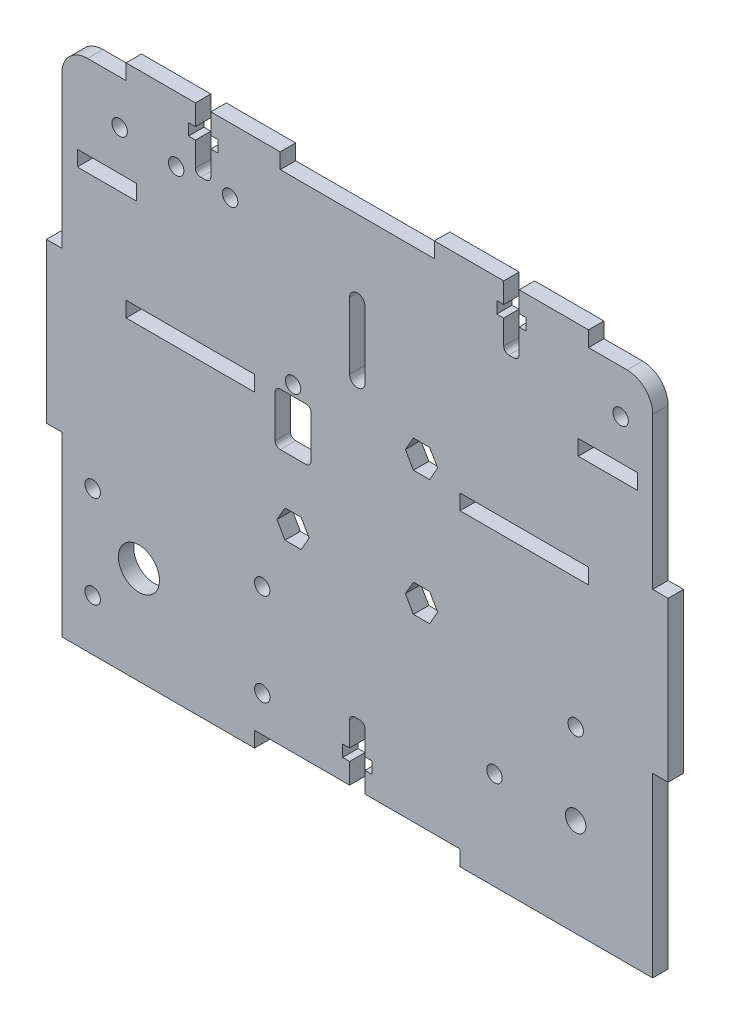
SolidWorks part; units mm, degrees
other "Marcação1"
sketch "Esboço7" plane through (-68, 31.5, 3) normal (-0.6758, 0.2828, 0.6807) x (0.7271, 0.1043, 0.6785)
sketch "Esboço8" plane through (-68, 31.5, 3) normal (-0.6758, 0.2828, 0.6807) x (0.7271, 0.1043, 0.6785)
sketch "Esboço9" plane through (-68, 31.5, 3) normal (-0.6758, 0.2828, 0.6807) x (0.7271, 0.1043, 0.6785)
sketch "Esboço10" plane through (-68, 31.5, 3) normal (-0.6758, 0.2828, 0.6807) x (0.7271, 0.1043, 0.6785)
sketch "Esboço11" plane through (-68, 36.25, 3) normal (-0.6758, 0.2828, 0.6807) x (0.7271, 0.1043, 0.6785)
sketch "Esboço13" plane through (-68, 36.25, 3) normal (-0.6758, 0.2828, 0.6807) x (0.7271, 0.1043, 0.6785)
sketch "Esboço15" plane through (-68, 36.25, 3) normal (-0.6758, 0.2828, 0.6807) x (0.7271, 0.1043, 0.6785)
sketch "Esboço19" plane through (-68, 66.25, 3) normal (-0.6758, 0.2828, 0.6807) x (0.7271, 0.1043, 0.6785)
sketch "Esboço22" plane through (-68, 95.5577, 3) normal (-0.6758, 0.2828, 0.6807) x (0.7271, 0.1043, 0.6785)
sketch "Sketch16" plane through (-60.5, 53, 1.5) normal (-0.6758, 0.2828, 0.6807) x (0.7271, 0.1043, 0.6785)
material "Acrylic (Medium-high impact)"
ref_plane "Plano frontal" through (0, 0, 0) normal (0, 0, 1) x (1, 0, 0)
ref_plane "Plano superior" through (0, 0, 0) normal (0, 1, 0) x (1, 0, 0)
ref_plane "Plano direito" through (0, 0, 0) normal (1, 0, 0) x (0, 0, -1)
sketch "Esboço1" plane through (0, 0, 0) normal (0, 0, 1) x (1, 0, 0)
  line L6 (57.5, -50) -> (-57.5, -50)
  line L8 (57.5, -50) -> (57.5, 50)
  line L9 (57.5, 50) -> (-57.5, 50)
  line L10 (-57.5, -50) -> (-57.5, 50)
  line L11 (57.5, -50) -> (-57.5, 50) construction
  line L12 (57.5, 50) -> (-57.5, -50) construction
  point P0 (0, 0)
  dimension "D1" = 100
  dimension "D2" = 115
extrude "Ressalto-extrusão1" add sketch "Esboço1" along normal mid plane 3
sketch "Esboço2" plane through (0, 0, 1.5) normal (0, 0, 1) x (1, 0, 0)
  line L1 (-20, -50) -> (20, -50)
  line L2 (-20, -50) -> (-20, -47)
  line L3 (-20, -47) -> (20, -47)
  line L4 (20, -50) -> (20, -47)
  line L6 (-57.5, -50) -> (57.5, -50) construction
  line L15 (57.5, 50) -> (-57.5, 50) construction
  line L25 (-45, 13) -> (-20, 13)
  line L26 (-45, 13) -> (-45, 10)
  line L29 (-45, 10) -> (-20, 10)
  line L30 (-20, 13) -> (-20, 10)
  line L31 (0, -1.65) -> (0, 1.65) construction
  line L32 (20, 13) -> (20, 10)
  line L33 (45, 10) -> (20, 10)
  line L34 (45, 13) -> (45, 10)
  line L35 (45, 13) -> (20, 13)
  point P6 (0, -47)
  dimension "D4" = 25
  dimension "D3" = 3
  dimension "D1" = 37
  dimension "D2" = 40
  dimension "D5" = 40
extrude "Corte-extrusão1" cut sketch "Esboço2" against normal through all
sketch "Sketch9" plane through (0, 0, 0) normal (0, 0, 1) x (1, 0, 0)
  line L0 (20, -47) -> (-20, -47) construction
  line L1 (-1.5, -47) -> (1.5, -47)
  line L2 (-1.5, -47) -> (-1.5, -43)
  line L3 (-0.5, -35) -> (0.5, -35)
  line L4 (1.5, -47) -> (1.5, -43)
  line L5 (1.5, -40.73) -> (2.85, -40.73)
  line L6 (-2.85, -40.73) -> (-1.5, -40.73)
  line L7 (-2.85, -40.73) -> (-2.85, -43)
  line L8 (-2.85, -43) -> (-1.5, -43)
  line L9 (2.85, -40.73) -> (2.85, -43)
  line L10 (-1.5, -40.73) -> (-1.5, -36)
  line L11 (1.5, -43) -> (2.85, -43)
  line L12 (1.5, -40.73) -> (1.5, -36)
  arc A0 (0.5, -35) -> (1.5, -36) centre (0.5, -36) cw
  arc A1 (-1.5, -36) -> (-0.5, -35) centre (-0.5, -36) cw
  point P6 (0, -35)
  point P18 (1.5, -35)
  point P21 (-1.5, -35)
  dimension "D7" = 1
  dimension "D1" = 3
  dimension "D2" = 12
  dimension "D3" = 2.27
  dimension "D4" = 1.35
  dimension "D5" = 1.35
  dimension "D6" = 4
extrude "Cut-Extrude12" cut sketch "Sketch9" against normal through all both and the other way through all
sketch "Esboço3" plane through (0, 0, 1.5) normal (0, 0, 1) x (1, 0, 0)
  line L0 (57.5, -50) -> (57.5, 50) construction
  line L1 (57.5, 15.5) -> (60.5, 15.5)
  line L2 (57.5, 15.5) -> (57.5, -15.5)
  line L3 (57.5, -15.5) -> (60.5, -15.5)
  line L4 (60.5, 15.5) -> (60.5, -15.5)
  line L5 (0, -1.65) -> (0, 1.65) construction
  line L6 (-57.5, -15.5) -> (-60.5, -15.5)
  line L7 (-57.5, 15.5) -> (-60.5, 15.5)
  line L8 (-57.5, 15.5) -> (-57.5, -15.5)
  line L9 (-60.5, 15.5) -> (-60.5, -15.5)
  line L15 (57.5, 50) -> (-57.5, 50) construction
  line L16 (-45, 50) -> (-15, 50)
  line L17 (-45, 50) -> (-45, 53)
  line L18 (-45, 53) -> (-15, 53)
  line L19 (-15, 50) -> (-15, 53)
  line L20 (15, 50) -> (15, 53)
  line L21 (45, 53) -> (15, 53)
  line L22 (45, 50) -> (45, 53)
  line L23 (45, 50) -> (15, 50)
  line L24 (-57.5, 50) -> (-57.5, -50) construction
  point P6 (57.5, 0)
  dimension "D1" = 3
  dimension "D2" = 31
  dimension "D3" = 30
  dimension "D4" = 15
  dimension "D5" = 12.5
extrude "Ressalto-extrusão2" add sketch "Esboço3" against normal through all
sketch "Esboço30" plane through (0, 0, -1.5) normal (0, 0, -1) x (-1, 0, 0)
  line L2 (57.5, -15.5) -> (57.5, -50) construction
  line L6 (57.5, -50) -> (20, -50) construction
  circle A1 centre (42.5, -31) radius 4
  dimension "D1" = 15
  dimension "D2" = 19
  dimension "D3" = 8
extrude "Corte-extrusão11" cut sketch "Esboço30" against normal through all both and the other way through all
sketch "Esboço4" plane through (0, 0, 1.5) normal (0, 0, 1) x (1, 0, 0)
  line L0 (57.5, -50) -> (57.5, -15.5) construction
  line L76 (-46.5, -31) -> (-38.5, -31) construction
  circle A11 centre (42.5, -31) radius 2
  circle A14 centre (-42.5, -31) radius 4 construction
  dimension "D1" = 15
  dimension "D2" = 4
extrude "Corte-extrusão2" cut sketch "Esboço4" against normal through all
sketch "Esboço31" plane through (0, 0, -1.5) normal (0, 0, -1) x (-1, 0, 0)
  line L1 (57.5, -15.5) -> (57.5, -50) construction
  line L2 (46.5, -31) -> (38.5, -31) construction
  circle A4 centre (51.5, -22) radius 1.5
  circle A5 centre (51.5, -40) radius 1.5
  circle A6 centre (42.5, -31) radius 4 construction
  circle A7 centre (18.5, -22) radius 1.5
  circle A8 centre (18.5, -40) radius 1.5
  dimension "D1" = 3
  dimension "D3" = 6
  dimension "D4" = 18
  dimension "D5" = 33
extrude "Corte-extrusão12" cut sketch "Esboço31" against normal through all both and the other way through all
sketch "Sketch8" [suppressed] plane through (0, 0, -1.5) normal (0, 0, -1) x (-1, 0, 0)
  line L31 (-57.5, 39.6519) -> (-53.4896, 39.6519)
  line L32 (-58, 31.6519) -> (-58, 23.6519) construction
  line L33 (-57.5, 23.6519) -> (-53.4896, 23.6519)
  line L34 (-45, 36.6519) -> (-45, 26.6519)
  line L35 (-57.5, 15.5) -> (-57.5, 50) construction
  line L37 (-48.5, 41.4019) -> (-50, 44)
  line L38 (-50, 44) -> (-53, 44)
  line L39 (-53, 44) -> (-54.5, 41.4019)
  line L40 (-54.5, 41.4019) -> (-53.4896, 39.6519)
  line L42 (-49.5104, 39.6519) -> (-48.5, 41.4019)
  line L43 (-49.5104, 39.6519) -> (-48, 39.6519)
  line L45 (-51.7693, 38.8038) -> (-50.2755, 38.8038) [skipped]
  line L46 (-58, 31.6519) -> (-45, 31.6519) construction
  line L48 (-49.5104, 23.6519) -> (-48.5, 21.9019)
  line L49 (-54.5, 21.9019) -> (-53.4896, 23.6519)
  line L50 (-53, 19.3038) -> (-54.5, 21.9019)
  line L51 (-50, 19.3038) -> (-53, 19.3038)
  line L52 (-48.5, 21.9019) -> (-50, 19.3038)
  line L53 (-49.5104, 23.6519) -> (-48, 23.6519)
  line L54 (-57.5, 23.6519) -> (-57.5, 39.6519)
  line L55 (-58, 39.6519) -> (-57.5, 39.6519) construction
  line L56 (-58, 39.6519) -> (-58, 31.6519) construction
  line L57 (-58, 23.6519) -> (-57.5, 23.6519) construction
  line L58 (-57.5, 50) -> (-45, 50) construction
  line L59 (0, 1.65) -> (0, -1.65) construction
  line L60 (58, 23.6519) -> (57.5, 23.6519) construction
  line L61 (58, 39.6519) -> (58, 31.6519) construction
  line L62 (58, 39.6519) -> (57.5, 39.6519) construction
  line L63 (58, 31.6519) -> (45, 31.6519) construction
  line L64 (58, 31.6519) -> (58, 23.6519) construction
  line L65 (57.5, 23.6519) -> (57.5, 39.6519)
  line L66 (49.5104, 23.6519) -> (48, 23.6519)
  line L67 (48.5, 21.9019) -> (50, 19.3038)
  line L68 (50, 19.3038) -> (53, 19.3038)
  line L69 (53, 19.3038) -> (54.5, 21.9019)
  line L70 (54.5, 21.9019) -> (53.4896, 23.6519)
  line L71 (49.5104, 23.6519) -> (48.5, 21.9019)
  line L72 (49.5104, 39.6519) -> (48, 39.6519)
  line L73 (49.5104, 39.6519) -> (48.5, 41.4019)
  line L74 (54.5, 41.4019) -> (53.4896, 39.6519)
  line L75 (53, 44) -> (54.5, 41.4019)
  line L76 (50, 44) -> (53, 44)
  line L77 (48.5, 41.4019) -> (50, 44)
  line L78 (45, 36.6519) -> (45, 26.6519)
  line L79 (57.5, 23.6519) -> (53.4896, 23.6519)
  line L80 (57.5, 39.6519) -> (53.4896, 39.6519)
  arc A10 (-48, 23.6519) -> (-45, 26.6519) centre (-48, 26.6519) ccw
  arc A12 (-48, 39.6519) -> (-45, 36.6519) centre (-48, 36.6519) cw
  arc A14 (-49.25, 40.1029) -> (-53.75, 40.1029) centre (-51.5, 41.4019) ccw construction
  arc A15 (-49.25, 23.201) -> (-53.75, 23.201) centre (-51.5, 21.9019) cw construction
  arc A16 (49.25, 23.201) -> (53.75, 23.201) centre (51.5, 21.9019) ccw construction
  arc A17 (49.25, 40.1029) -> (53.75, 40.1029) centre (51.5, 41.4019) cw construction
  arc A18 (48, 39.6519) -> (45, 36.6519) centre (48, 36.6519) ccw
  arc A19 (48, 23.6519) -> (45, 26.6519) centre (48, 26.6519) cw
  point P9 (-45, 23.6519)
  point P14 (-45, 39.6519)
  point P17 (-58, 39.6519)
  point P38 (-51.5, 31.6519)
  point P73 (45, 39.6519)
  point P74 (45, 23.6519)
  dimension "D1" = 13
  dimension "D2" = 3
  dimension "D5" = 3
  dimension "D6" = 3
  dimension "D3" = 16
  dimension "D7" = 19.5
  dimension "D8" = 6
sketch "Sketch11" plane through (0, 0, 0) normal (0, 0, 1) x (1, 0, 0)
  line L0 (45, 53) -> (15, 53) construction
  line L1 (28.5, 53) -> (31.5, 53)
  line L2 (28.5, 53) -> (28.5, 49)
  line L3 (29.5, 41) -> (30.5, 41)
  line L4 (31.5, 53) -> (31.5, 49)
  line L5 (15, 53) -> (15, 50) construction
  line L6 (28.5, 46.73) -> (28.5, 42)
  line L7 (27.15, 49) -> (28.5, 49)
  line L8 (27.15, 49) -> (27.15, 46.73)
  line L9 (27.15, 46.73) -> (28.5, 46.73)
  line L10 (32.85, 49) -> (32.85, 46.73)
  line L11 (31.5, 49) -> (32.85, 49)
  line L12 (31.5, 46.73) -> (31.5, 42)
  line L13 (31.5, 46.73) -> (32.85, 46.73)
  line L27 (0, -1.65) -> (0, 1.65) construction
  line L28 (-31.5, 46.73) -> (-32.85, 46.73)
  line L29 (-31.5, 46.73) -> (-31.5, 42)
  line L30 (-31.5, 49) -> (-32.85, 49)
  line L31 (-32.85, 49) -> (-32.85, 46.73)
  line L32 (-27.15, 46.73) -> (-28.5, 46.73)
  line L33 (-27.15, 49) -> (-27.15, 46.73)
  line L34 (-27.15, 49) -> (-28.5, 49)
  line L35 (-28.5, 46.73) -> (-28.5, 42)
  line L36 (-31.5, 53) -> (-31.5, 49)
  line L37 (-29.5, 41) -> (-30.5, 41)
  line L38 (-28.5, 53) -> (-28.5, 49)
  line L39 (-28.5, 53) -> (-31.5, 53)
  arc A0 (30.5, 41) -> (31.5, 42) centre (30.5, 42) ccw
  arc A1 (28.5, 42) -> (29.5, 41) centre (29.5, 42) ccw
  arc A4 (-28.5, 42) -> (-29.5, 41) centre (-29.5, 42) cw
  arc A5 (-30.5, 41) -> (-31.5, 42) centre (-30.5, 42) cw
  point P20 (28.5, 41)
  point P39 (-28.5, 41)
  dimension "D8" = 1
  dimension "D1" = 3
  dimension "D2" = 12
  dimension "D3" = 13.5
  dimension "D4" = 1.35
  dimension "D5" = 2.27
  dimension "D6" = 1.35
  dimension "D7" = 4
extrude "Cut-Extrude14" cut sketch "Sketch11" against normal through all both and the other way through all
sketch "Sketch13" plane through (0, 0, 0) normal (0, 0, 1) x (1, 0, 0)
  line L18 (-10, 13.0193) -> (-15, 13.0193)
  line L19 (-9, 12.0193) -> (-9, 3.8193)
  line L20 (-10, 2.8193) -> (-15, 2.8193)
  line L21 (-16, 12.0193) -> (-16, 3.8193)
  line L23 (15.64, 15.0193) -> (14.07, 17.7386)
  line L24 (14.07, 17.7386) -> (10.93, 17.7386)
  line L25 (10.93, 17.7386) -> (9.36, 15.0193)
  line L26 (9.36, 15.0193) -> (10.93, 12.3)
  line L27 (10.93, 12.3) -> (14.07, 12.3)
  line L28 (14.07, 12.3) -> (15.64, 15.0193)
  line L30 (15.64, -9.2807) -> (14.07, -6.5614)
  line L31 (14.07, -6.5614) -> (10.93, -6.5614)
  line L32 (10.93, -6.5614) -> (9.36, -9.2807)
  line L33 (9.36, -9.2807) -> (10.93, -12)
  line L34 (10.93, -12) -> (14.07, -12)
  line L35 (14.07, -12) -> (15.64, -9.2807)
  line L38 (-9.36, -9.2807) -> (-10.93, -6.5614)
  line L39 (-10.93, -6.5614) -> (-14.07, -6.5614)
  line L40 (-14.07, -6.5614) -> (-15.64, -9.2807)
  line L41 (-15.64, -9.2807) -> (-14.07, -12)
  line L42 (-14.07, -12) -> (-10.93, -12)
  line L43 (-10.93, -12) -> (-9.36, -9.2807)
  line L45 (-12.5, 15.0193) -> (12.5, 15.0193) construction
  circle A1 centre (12.5, 15.0193) radius 1.5 construction
  circle A2 centre (-12.5, -9.2807) radius 1.5 construction
  circle A3 centre (12.5, -9.2807) radius 1.5 construction
  circle A10 centre (-12.5, 15.0193) radius 1.5
  arc A11 (-15, 2.8193) -> (-16, 3.8193) centre (-15, 3.8193) cw
  arc A12 (-9, 3.8193) -> (-10, 2.8193) centre (-10, 3.8193) cw
  arc A13 (-15, 13.0193) -> (-16, 12.0193) centre (-15, 12.0193) ccw
  arc A14 (-10, 13.0193) -> (-9, 12.0193) centre (-10, 12.0193) cw
  circle A15 centre (12.5, 15.0193) radius 2.7193 construction
  circle A16 centre (12.5, -9.2807) radius 2.7193 construction
  circle A17 centre (-12.5, -9.2807) radius 2.7193 construction
  circle A18 centre (-18.5, -22) radius 1.5 construction
  point P10 (0, 15.0193)
  point P16 (-12.5, 13.0193)
  point P19 (-16, 2.8193)
  point P25 (-16, 13.0193)
  dimension "D1" = 3
  dimension "D3" = 25
  dimension "D2" = 24.3
  dimension "D6" = 0.5
  dimension "D4" = 8.5
  dimension "D9" = 1
  dimension "D10" = 3.14
  dimension "D7" = 10.2
  dimension "D8" = 2
extrude "Cut-Extrude16" cut sketch "Sketch13" against normal through all both and the other way through all
sketch "Sketch12" plane through (0, 0, -1.5) normal (0, 0, 1) x (1, 0, 0)
  line L3 (0, 22.2386) -> (0, 35.2386) construction
  line L6 (-1.5, 22.2386) -> (-1.5, 35.2386)
  line L7 (1.5, 22.2386) -> (1.5, 35.2386)
  line L8 (-2, 23.2803) -> (-6, 23.2803)
  line L9 (-2, 22.2386) -> (-6, 22.2386)
  line L10 (-2, 22.2386) -> (-2, 22.7386)
  line L11 (-2, 22.7386) -> (-6, 22.7386)
  line L12 (-6, 22.2386) -> (-6, 22.7386)
  line L13 (-2, 23.2803) -> (-2, 23.7803)
  line L14 (-2, 23.7803) -> (-6, 23.7803)
  line L15 (-6, 23.2803) -> (-6, 23.7803)
  line L16 (-2, 24.322) -> (-6, 24.322)
  line L17 (-2, 24.322) -> (-2, 24.822)
  line L18 (-2, 24.822) -> (-6, 24.822)
  line L19 (-6, 24.322) -> (-6, 24.822)
  line L20 (-2, 25.3636) -> (-6, 25.3636)
  line L21 (-2, 25.3636) -> (-2, 25.8636)
  line L22 (-2, 25.8636) -> (-6, 25.8636)
  line L23 (-6, 25.3636) -> (-6, 25.8636)
  line L24 (-2, 26.4053) -> (-6, 26.4053)
  line L25 (-2, 26.4053) -> (-2, 26.9053)
  line L26 (-2, 26.9053) -> (-6, 26.9053)
  line L27 (-6, 26.4053) -> (-6, 26.9053)
  line L28 (-2, 27.447) -> (-6, 27.447)
  line L29 (-2, 27.447) -> (-2, 27.947)
  line L30 (-2, 27.947) -> (-6, 27.947)
  line L31 (-6, 27.447) -> (-6, 27.947)
  line L32 (-2, 28.4886) -> (-6, 28.4886)
  line L33 (-2, 28.4886) -> (-2, 28.9886)
  line L34 (-2, 28.9886) -> (-6, 28.9886)
  line L35 (-6, 28.4886) -> (-6, 28.9886)
  line L36 (-2, 29.5303) -> (-6, 29.5303)
  line L37 (-2, 29.5303) -> (-2, 30.0303)
  line L38 (-2, 30.0303) -> (-6, 30.0303)
  line L39 (-6, 29.5303) -> (-6, 30.0303)
  line L40 (-2, 30.572) -> (-6, 30.572)
  line L41 (-2, 30.572) -> (-2, 31.072)
  line L42 (-2, 31.072) -> (-6, 31.072)
  line L43 (-6, 30.572) -> (-6, 31.072)
  line L44 (-2, 31.6136) -> (-6, 31.6136)
  line L45 (-2, 31.6136) -> (-2, 32.1136)
  line L46 (-2, 32.1136) -> (-6, 32.1136)
  line L47 (-6, 31.6136) -> (-6, 32.1136)
  line L48 (-2, 32.6553) -> (-6, 32.6553)
  line L49 (-2, 32.6553) -> (-2, 33.1553)
  line L50 (-2, 33.1553) -> (-6, 33.1553)
  line L51 (-6, 32.6553) -> (-6, 33.1553)
  line L52 (-2, 33.697) -> (-6, 33.697)
  line L53 (-2, 33.697) -> (-2, 34.197)
  line L54 (-2, 34.197) -> (-6, 34.197)
  line L55 (-6, 33.697) -> (-6, 34.197)
  line L56 (-2, 34.7386) -> (-6, 34.7386)
  line L57 (-2, 34.7386) -> (-2, 35.2386)
  line L58 (-2, 35.2386) -> (-6, 35.2386)
  line L59 (-6, 34.7386) -> (-6, 35.2386)
  line L66 (14.07, 17.7386) -> (10.93, 17.7386) construction
  circle A1 centre (0, 22.2386) radius 1.5 construction
  arc A4 (-1.5, 22.2386) -> (1.5, 22.2386) centre (0, 22.2386) ccw
  arc A5 (1.5, 35.2386) -> (-1.5, 35.2386) centre (0, 35.2386) ccw
  point P4 (0, 28.7386)
  dimension "D1" = 3
  dimension "D2" = 13
  dimension "D3" = 0.5
  dimension "D4" = 3
  dimension "D5" = 4
  dimension "D6" = 0.5
  dimension "D7" = 13
extrude "Cut-Extrude15" cut sketch "Sketch12" along normal through all contours L7 A5 L6 A4 | A5 L7 A4 L6 region at (0, 28.7386, -1.5)
extrude "Cut-Extrude18" cut sketch "Sketch12<3>" along normal blind 0.1 contours L59 L56 L57 L58 | L55 L52 L53 L54 | L51 L48 L49 L50 | L47 L44 L45 L46 | L39 L36 L37 L38 | L43 L40 L41 L42 | L31 L28 L29 L30 | L35 L32 L33 L34 | L27 L24 L25 L26 | L23 L20 L21 L22 | L19 L16 L17 L18 | L15 L8 L13 L14 | L12 L9 L10 L11 | L56 L59 L58 L57 | L52 L55 L54 L53 | L48 L51 L50 L49 | L44 L47 L46 L45 | L40 L43 L42 L41 | L36 L39 L38 L37 | L32 L35 L34 L33 | L28 L31 L30 L29 | L24 L27 L26 L25 | L20 L23 L22 L21 | L16 L19 L18 L17 | L8 L15 L14 L13 | L9 L12 L11 L10 | L42 L43 L40 L41 | L38 L39 L36 L37 region at (-4, 23.5303, -1.5) region at (-4, 22.4886, -1.5) region at (-4, 24.572, -1.5) region at (-4, 25.6136, -1.5) region at (-4, 26.6553, -1.5) region at (-4, 27.697, -1.5) region at (-4, 28.7386, -1.5) region at (-4, 29.7803, -1.5) region at (-4, 30.822, -1.5) region at (-4, 31.8636, -1.5) region at (-4, 32.9053, -1.5) region at (-4, 33.947, -1.5) region at (-4, 34.9886, -1.5)
sketch "Sketch12<3>" plane through (0, 0, -1.5) normal (0, 0, 1) x (1, 0, 0) same geometry as "Sketch12"
fillet "Fillet1" radius 5 2 edges at (57.5, 50, 0) (-57.5, 50, 0)
sketch "Sketch14" plane through (0, 0, 0) normal (0, 0, 1) x (1, 0, 0)
  line L0 (-30, 42.1706) -> (-30, 58.8294) construction
  line L1 (-45, 53) -> (-15, 53) construction
  line L3 (15, 50) -> (-15, 50) construction
  circle A0 centre (-24.75, 40.4) radius 1.5
  circle A1 centre (-35.25, 40.4) radius 1.5
  point P5 (-30, 53)
  point P7 (-30, 53)
  dimension "D1" = 3
  dimension "D2" = 10.5
  dimension "D3" = 9.6
extrude "Cut-Extrude17" cut sketch "Sketch14" against normal through all both and the other way through all
extrude "Cut-Extrude19" [suppressed] cut sketch "Sketch8" against normal through all both and the other way through all
fillet "Fillet3" [suppressed] radius 1.5
sketch "Sketch15" plane through (0, 0, 0) normal (0, 0, 1) x (1, 0, 0)
  line L0 (57.5, 15.5) -> (57.5, 45) construction
  line L1 (54.5, 33.7) -> (43, 33.7)
  line L2 (54.5, 33.7) -> (54.5, 30.7)
  line L3 (54.5, 30.7) -> (43, 30.7)
  line L4 (43, 33.7) -> (43, 30.7)
  line L5 (52.5, 50) -> (45, 50) construction
  line L6 (0, -1.65) -> (0, 1.65) construction
  line L7 (-43, 33.7) -> (-43, 30.7)
  line L8 (-54.5, 30.7) -> (-43, 30.7)
  line L9 (-54.5, 33.7) -> (-54.5, 30.7)
  line L10 (-54.5, 33.7) -> (-43, 33.7)
  circle A0 centre (51.25, 41.5) radius 1.5
  circle A2 centre (-46.25, 41.5) radius 1.5
  point P8 (48.75, 33.7)
  point P20 (-48.75, 33.7)
  dimension "D4" = 3
  dimension "D7" = 7
  dimension "D8" = 2.5
  dimension "D1" = 11.5
  dimension "D2" = 3
  dimension "D3" = 3
  dimension "D5" = 7.8
  dimension "D6" = 2.5
extrude "Corte GY-53LDK" cut sketch "Sketch15" against normal through all both and the other way through all
sketch "Sketch17" plane through (0, 0, -1.5) normal (0, 0, -1) x (-1, 0, 0)
  circle A0 centre (-42.5, -15.2) radius 1.5
  circle A1 centre (-26.7, -31) radius 1.5
  dimension "D1" = 3
extrude "Cut-Extrude20" cut sketch "Sketch17" against normal through all both and the other way through all
